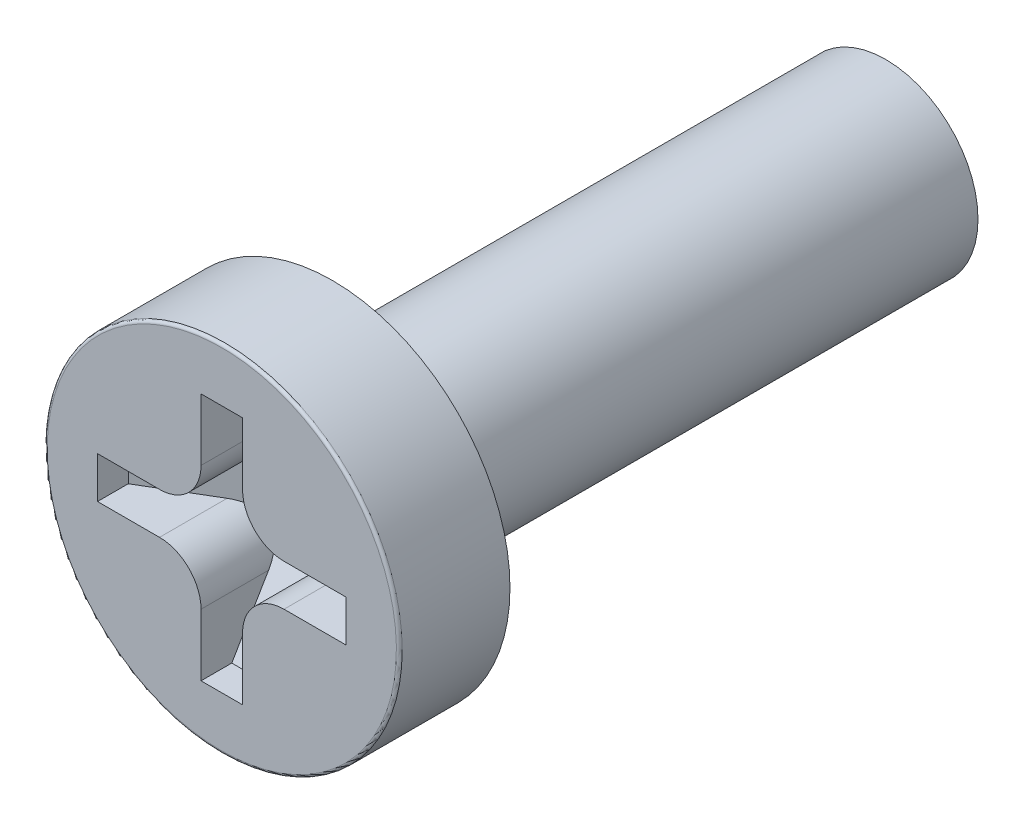
SolidWorks part; units mm, degrees
ref_plane "前视基准面" through (0, 0, 0) normal (0, 0, 1) x (1, 0, 0)
ref_plane "上视基准面" through (0, 0, 0) normal (0, 1, 0) x (1, 0, 0)
ref_plane "右视基准面" through (0, 0, 0) normal (1, 0, 0) x (0, 0, -1)
ref_plane "基准面1" through (0, 0, 0) normal (0, -1, 0) x (1, 0, 0)
sketch "草图1" plane through (0, 0, 0) normal (0, -1, 0) x (1, 0, 0)
  line L0 (1.925, 1.2) -> (0, 1.2)
  line L1 (0, 1.2) -> (0, 0)
  line L2 (0, 0) -> (1.925, 0)
  line L3 (1.925, 0) -> (1.925, 1.2)
  line L4 (0, 1.2) -> (0, 0) construction
revolve "旋转1" add sketch "草图1" angle 360 about L4 reverse direction yes
sketch "草图2" plane through (0, 0, 1.2) normal (0, 0, 1) x (1, 0, 0)
  line L0 (0.225, 1.3475) -> (-0.225, 1.3475)
  line L1 (-0.225, 1.3475) -> (-0.225, 0.225)
  line L2 (-0.225, 0.225) -> (-1.3475, 0.225)
  line L3 (-1.3475, 0.225) -> (-1.3475, -0.225)
  line L4 (-1.3475, -0.225) -> (-0.225, -0.225)
  line L5 (-0.225, -0.225) -> (-0.225, -1.3475)
  line L6 (-0.225, -1.3475) -> (0.225, -1.3475)
  line L7 (0.225, -1.3475) -> (0.225, -0.225)
  line L8 (0.225, -0.225) -> (1.3475, -0.225)
  line L9 (1.3475, -0.225) -> (1.3475, 0.225)
  line L10 (1.3475, 0.225) -> (0.225, 0.225)
  line L11 (0.225, 0.225) -> (0.225, 1.3475)
extrude "切除-拉伸1" cut sketch "草图2" against normal blind 1
sketch "草图3" plane through (0, 0.225, 0) normal (0, -1, 0) x (1, 0, 0)
  line L0 (-0.45, 0.3336) -> (-0.45, 0.2)
  line L1 (-0.45, 0.2) -> (-1.3475, 0.2)
  line L2 (-1.3475, 0.2) -> (-1.3475, 0.3336)
  line L3 (-1.3475, 0.3336) -> (-0.45, 0.3336)
extrude "凸台-拉伸1" add sketch "草图3" along normal blind 0.45
sketch "草图4" plane through (-0.225, 0, 0) normal (1, 0, 0) x (0, 0, -1)
  line L0 (-0.3336, 1.3475) -> (-0.2, 1.3475)
  line L1 (-0.2, 1.3475) -> (-0.2, 0.45)
  line L2 (-0.2, 0.45) -> (-0.3336, 0.45)
  line L3 (-0.3336, 0.45) -> (-0.3336, 1.3475)
extrude "凸台-拉伸2" add sketch "草图4" along normal blind 0.45
sketch "草图5" plane through (0, 0.225, 0) normal (0, -1, 0) x (1, 0, 0)
  line L0 (1.3475, 0.3336) -> (1.3475, 0.2)
  line L1 (1.3475, 0.2) -> (0.45, 0.2)
  line L2 (0.45, 0.2) -> (0.45, 0.3336)
  line L3 (0.45, 0.3336) -> (1.3475, 0.3336)
extrude "凸台-拉伸3" add sketch "草图5" along normal blind 0.45
sketch "草图6" plane through (-0.225, 0, 0) normal (1, 0, 0) x (0, 0, -1)
  line L0 (-0.3336, -0.45) -> (-0.2, -0.45)
  line L1 (-0.2, -0.45) -> (-0.2, -1.3475)
  line L2 (-0.2, -1.3475) -> (-0.3336, -1.3475)
  line L3 (-0.3336, -1.3475) -> (-0.3336, -0.45)
extrude "凸台-拉伸4" add sketch "草图6" along normal blind 0.45
sketch "草图7" plane through (0, 0, 0) normal (0, 0, -1) x (-1, 0, 0)
  circle A0 centre (0, 0) radius 1
extrude "凸台-拉伸5" add sketch "草图7" along normal blind 6
draft "拔模1" type of draft neutral plane draft angle 30.707 faces to draft 1 face at (0, 0.8988, 0.3336) neutral plane through (0.225, 0.45, 0.2) neutral plane normal (0, -1, 0) parameters "D1"=30.707
draft "拔模2" type of draft neutral plane draft angle 30.707 faces to draft 1 face at (0.8987, 0, 0.3336) neutral plane through (0.45, -0.225, 0.2) neutral plane normal (-1, 0, 0) parameters "D1"=30.707
draft "拔模3" type of draft neutral plane draft angle 30.707 faces to draft 1 face at (0, -0.8987, 0.3336) neutral plane through (0.225, -0.45, 0.3336) neutral plane normal (0, 1, 0) parameters "D1"=30.707
draft "拔模4" type of draft neutral plane draft angle 30.707 faces to draft 1 face at (-0.8988, 0, 0.3336) neutral plane through (-0.45, -0.225, 0.3336) neutral plane normal (1, 0, 0) parameters "D1"=30.707
fillet "圆角1" radius 0.0315 1 edges at (0, 1.925, 1.2) tangent propagation no
fillet "圆角2" radius 0.45 4 edges at (0.225, 0.225, 0.7) (0.225, -0.225, 0.7) (-0.225, 0.225, 0.7) (-0.225, -0.225, 0.7) tangent propagation no
